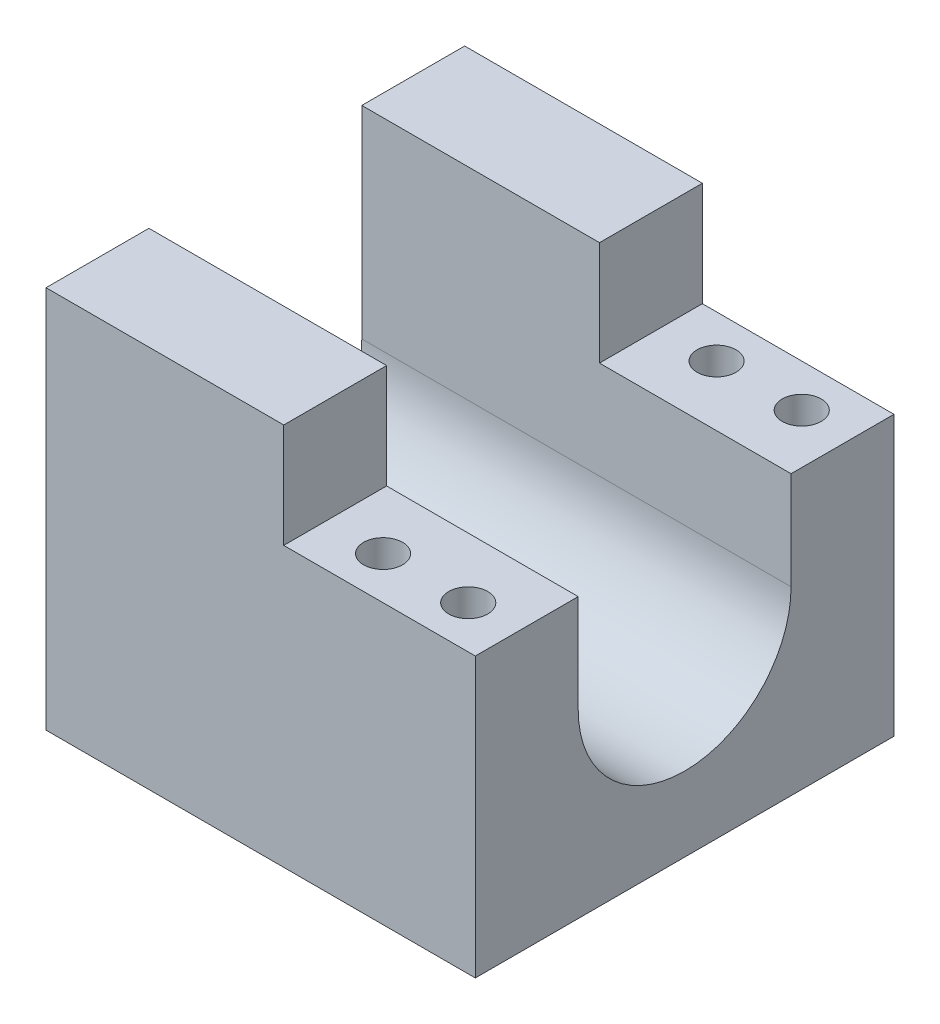
SolidWorks part; units mm, degrees
ref_plane "Front Plane" through (0, 0, 0) normal (0, 0, 1) x (1, 0, 0)
ref_plane "Top Plane" through (0, 0, 0) normal (0, 1, 0) x (1, 0, 0)
ref_plane "Right Plane" through (0, 0, 0) normal (1, 0, 0) x (0, 0, -1)
sketch "Sketch1" plane through (0, 0, 0) normal (0, 0, 1) x (1, 0, 0)
  line L1 (60.5, 22.7) -> (60.5, 50.3)
  line L2 (60.5, 50.3) -> (58.5, 50.3)
  line L3 (60.5, 22.7) -> (60.5, 8)
  line L4 (60.5, 8) -> (33.5, 8)
  line L6 (10, 8) -> (0, 8)
  line L8 (0, 8) -> (0, 65)
  line L9 (33.5, 50.3) -> (33.5, 65)
  line L10 (33.5, 50.3) -> (58.5, 50.3)
  line L11 (10, 8) -> (33.5, 8)
  line L13 (10, 65) -> (33.5, 65)
  line L18 (0, 65) -> (10, 65)
extrude "Boss-Extrude1" add sketch "Sketch1" against normal blind 59
sketch "Sketch2" plane through (0, 0, 0) normal (-1, 0, 0) x (0, 0, 1)
  circle A0 centre (-6, 13) radius 1.65
  circle A1 centre (-6, 60) radius 1.65
  circle A2 centre (-53, 13) radius 1.65
  circle A3 centre (-53, 60) radius 1.65
  dimension "D1" = 2
extrude "Cut-Extrude1" cut sketch "Sketch2" against normal blind 30
sketch "Sketch3" plane through (0, 8, 0) normal (0, -1, 0) x (1, 0, 0)
  circle A0 centre (53.5, -6) radius 5
  circle A1 centre (41.5, -6) radius 5
  circle A2 centre (41.5, -53) radius 5
  circle A3 centre (53.5, -53) radius 5
  dimension "D1" = 2
hole_wizard "CBORE for M5 SHCS1" positions "Sketch4" profile "Sketch6" counterbore size "M5" standard "ANSI Metric"
sketch "Sketch4" plane through (0, 8, 0) normal (0, -1, 0) x (-1, 0, 0)
  point P0 (-53.5, 6)
  point P3 (-41.5, 6)
  point P6 (-41.5, 53)
  point P9 (-53.5, 53)
sketch "Sketch6" plane through (53.5, 8, -6) normal (1, 0, 0) x (0, 0, -1)
  line L0 (0, 0) -> (0, 100)
  line L1 (0, 100) -> (2.75, 98.3476)
  line L2 (2.75, 98.3476) -> (2.75, 5)
  line L3 (2.75, 5) -> (5, 5)
  line L4 (5, 5) -> (5, 0)
  line L5 (5, 0) -> (0, 0)
  line L10 (0, 100) -> (-2.75, 98.3476) construction
  line L11 (0, -6.35) -> (0, 107.95) construction
  dimension "Hole Dia." = 5.5
  dimension "Hole Depth" = 100
  dimension "C'Bore Dia." = 10
  dimension "C'Bore Depth" = 5
  dimension "Drill Angle" = 118
sketch "Sketch7" plane through (0, 0, 0) normal (-1, 0, 0) x (0, 0, 1)
  line L1 (-14.5, 36.5) -> (-14.5, 65)
  line L2 (-59, 65) -> (0, 65) construction
  line L3 (-14.5, 65) -> (-44.5, 65)
  line L4 (-44.5, 65) -> (-44.5, 36.5)
  arc A0 (-44.5, 36.5) -> (-14.5, 36.5) centre (-29.5, 36.5) ccw
extrude "Cut-Extrude2" cut sketch "Sketch7" against normal through all
chamfer "Chamfer1" distance 3 angle 45 8 edges at (60.5, 8, -29.5) (30.25, 8, -59) (0, 8, -29.5) (30.25, 8, 0) (53.5, 8, -58) (41.5, 8, -58) (41.5, 8, -11) (53.5, 8, -11)
